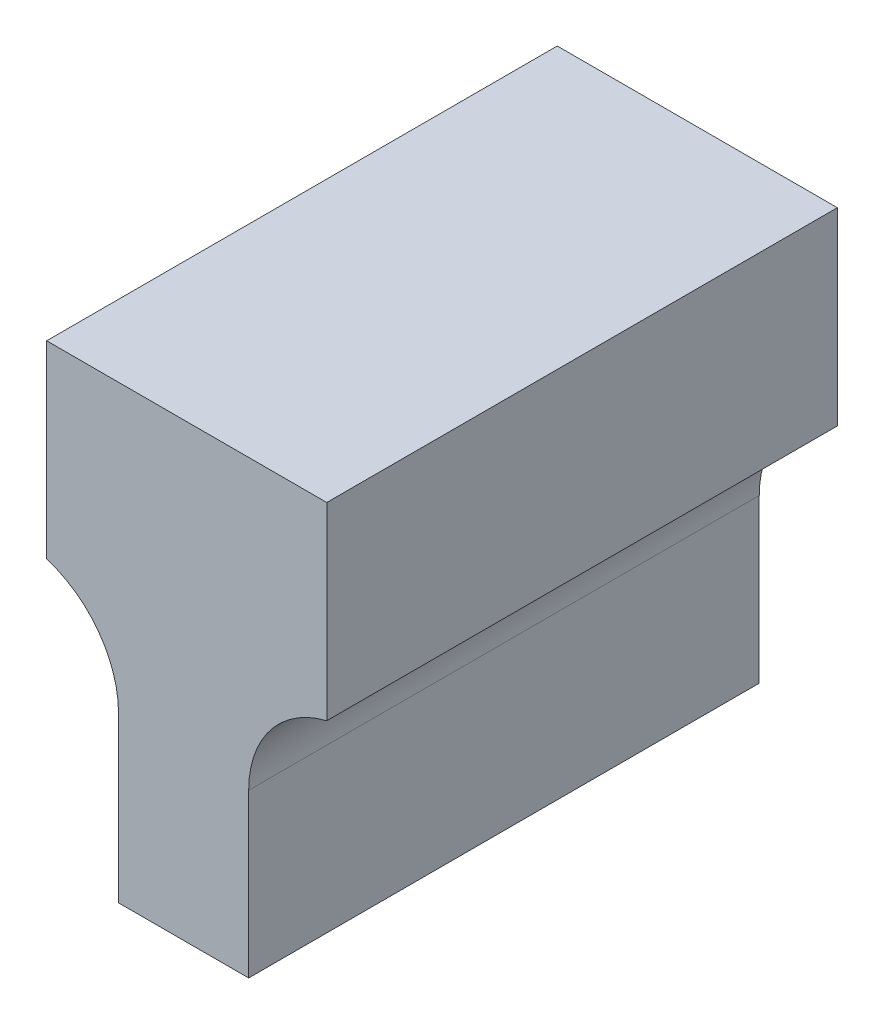
SolidWorks part; units mm, degrees
ref_plane "Front" through (0, 0, 0) normal (0, 0, 1) x (1, 0, 0)
ref_plane "Top" through (0, 0, 0) normal (0, 1, 0) x (1, 0, 0)
ref_plane "Right" through (0, 0, 0) normal (1, 0, 0) x (0, 0, -1)
sketch "Sketch3" plane through (0, 0, 0) normal (0, 0, 1) x (1, 0, 0)
  line L1 (0, 0) -> (5.4857, 0)
  line L2 (0, 0) -> (0, 3.702)
  line L3 (0, 3.702) -> (5.4857, 3.702)
  line L4 (5.4857, 0) -> (5.4857, 3.702)
  line L5 (1.4074, 0) -> (3.9563, 0)
  line L6 (1.4074, 0) -> (1.4074, -5.1282)
  line L7 (1.4074, -5.1282) -> (3.9563, -5.1282)
  line L8 (3.9563, 0) -> (3.9563, -5.1282)
extrude "Boss-Extrude2" add sketch "Sketch3" along normal blind 10 contours L1 L4 L3 L2 | L8 L1 L6 L7 region at (2.7428, 1.851, 0) region at (2.6819, -2.5641, 0)
fillet "Fillet1" radius 2 2 edges at (3.9563, 0, 5) (1.4074, 0, 5)
